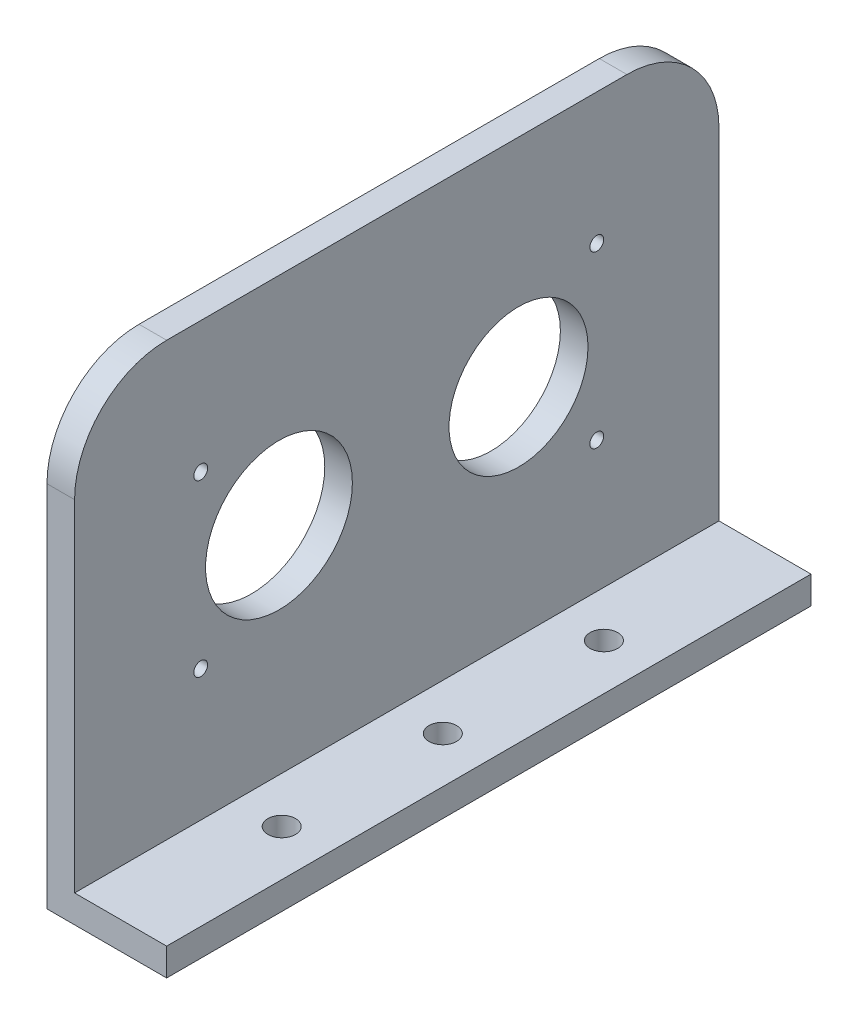
SolidWorks part; units mm, degrees
ref_plane "Front Plane" through (0, 0, 0) normal (0, 0, 1) x (1, 0, 0)
ref_plane "Top Plane" through (0, 0, 0) normal (0, 1, 0) x (1, 0, 0)
ref_plane "Right Plane" through (0, 0, 0) normal (1, 0, 0) x (0, 0, -1)
sketch "Sketch1" plane through (0, 0, 0) normal (0, 0, 1) x (1, 0, 0)
  line L0 (0, 0) -> (0, 3)
  line L1 (0, 3) -> (-10, 3)
  line L2 (-10, 3) -> (-10, 50)
  line L3 (-10, 50) -> (-13, 50)
  line L4 (-13, 50) -> (-13, 0)
  line L5 (-13, 0) -> (0, 0)
  dimension "D1" = 50
  dimension "D2" = 3
  dimension "D3" = 3
  dimension "D4" = 10
extrude "Boss-Extrude1" add sketch "Sketch1" along normal blind 70 contours L4 L5 L0 L1 L2 L3
sketch "Sketch2" plane through (-10, 0, 0) normal (1, 0, 0) x (0, 0, -1)
  line L0 (-31.1498, 39) -> (-31.1498, 50) construction
  line L1 (-60, 39) -> (-10, 39)
  line L2 (-60, 39) -> (-60, 14)
  line L3 (-60, 14) -> (-10, 14)
  line L4 (-10, 39) -> (-10, 14)
  line L5 (-70, 50) -> (0, 50) construction
  line L6 (-26.3251, 14) -> (-26.3251, 3) construction
  line L7 (-70, 3) -> (0, 3) construction
  line L8 (-10, 28.025) -> (0, 28.025) construction
  line L9 (0, 3) -> (0, 50) construction
  line L10 (-60, 26.6465) -> (-70, 26.6465) construction
  line L11 (-70, 3) -> (-70, 50) construction
  line L13 (-39.8225, 26.5) -> (-29.3225, 26.5) construction
  line L14 (-14.2275, 26.5) -> (-10, 26.5) construction
  line L15 (-55.7725, 26.5) -> (-60, 26.5) construction
  circle A0 centre (-47.7975, 26.5) radius 7.975
  circle A1 centre (-21.775, 26.5) radius 7.5475
  dimension "D3" = 15.95
  dimension "D4" = 15.095
  dimension "D1" = 50
  dimension "D2" = 25
  dimension "D5" = 10.5
  dimension "D6" = 26.0225
extrude "Cut-Extrude9" cut sketch "Sketch2" against normal through all contours A0
extrude "Cut-Extrude10" cut sketch "Sketch2<12>" against normal through all contours A1
sketch "Sketch2<12>" plane through (-10, 0, 0) normal (1, 0, 0) x (0, 0, -1) same geometry as "Sketch2"
fillet "Fillet1" radius 10 1 edges at (-11.5, 50, 70) type face fillet first side face at (-11.5, 50, 35) second side face at (-7.6667, 17.6667, 70)
fillet "Fillet2" radius 10 1 edges at (-11.5, 50, 0) type face fillet first side face at (-11.5, 50, 30) second side face at (-7.6667, 17.6667, 0)
sketch "Sketch3" plane through (0, 3, 0) normal (0, 1, 0) x (1, 0, 0)
  line L0 (-5, 0) -> (-5, -70) construction
  line L1 (0, 0) -> (-10, 0) construction
  line L2 (0, -70) -> (-10, -70) construction
  circle A0 centre (-5, -35) radius 1.5
  circle A1 centre (-5, -52.5) radius 1.5
  circle A2 centre (-5, -17.5) radius 1.5
  dimension "D1" = 17.5
  dimension "D2" = 17.5
  dimension "D3" = 3
  dimension "D4" = 17.5
  dimension "D5" = 3
  dimension "D6" = 3
extrude "Cut-Extrude11" cut sketch "Sketch3" against normal through all
sketch "Sketch4" plane through (-13, 0, 0) normal (-1, 0, 0) x (0, 0, 1)
  circle A0 centre (56.2975, 35.75) radius 0.75
  circle A1 centre (13.275, 35.75) radius 0.75
  circle A2 centre (13.275, 17.25) radius 0.75
  circle A3 centre (56.2975, 17.25) radius 0.75
  circle A4 centre (21.775, 26.5) radius 7.5475 construction
  circle A5 centre (47.7975, 26.5) radius 7.975 construction
  dimension "D1" = 9.25
  dimension "D5" = 8.5
  dimension "D6" = 8.5
  dimension "D7" = 8.5
  dimension "D8" = 8.5
  dimension "D9" = 1.5
  dimension "D10" = 1.5
  dimension "D11" = 1.5
  dimension "D12" = 1.5
  dimension "D2" = 9.25
  dimension "D3" = 9.25
  dimension "D4" = 9.25
extrude "Cut-Extrude12" cut sketch "Sketch4" against normal through all
